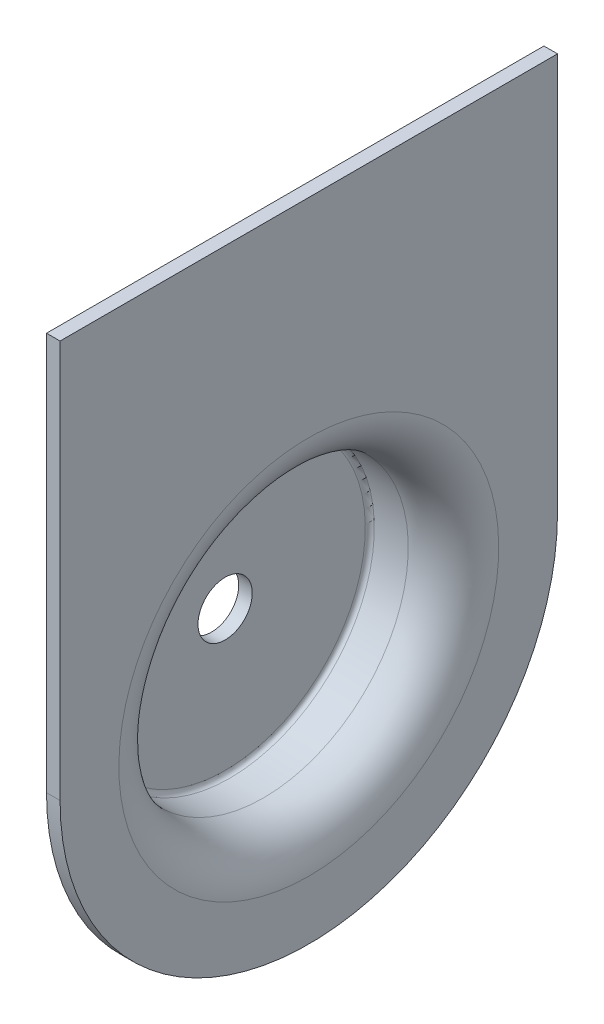
SolidWorks part; units mm, degrees
material "ABS"
ref_plane "Front Plane" through (0, 0, 0) normal (0, 0, 1) x (1, 0, 0)
ref_plane "Top Plane" through (0, 0, 0) normal (0, 1, 0) x (1, 0, 0)
ref_plane "Right Plane" through (0, 0, 0) normal (1, 0, 0) x (0, 0, -1)
sketch "Sketch1" plane through (-42.5, 0, 0) normal (1, 0, 0) x (0, 0, -1)
  circle A0 centre (50, -18.3727) radius 32
  arc A1 (50, 46.3864) -> (50, -83.1319) centre (50, -18.3727) ccw construction
  circle A6 centre (50, -18.3727) radius 31.5 construction
  circle A7 centre (50, -18.3727) radius 35
  dimension "D1" = 0.5
  dimension "D2" = 3
extrude "MOTOR RING" add sketch "Sketch1" against normal blind 6 and the other way offset from surface (12.5 mm away) 3
sketch "Sketch3" plane through (-48.5, 0, 0) normal (1, 0, 0) x (0, 0, -1)
  circle A0 centre (50, -18.3727) radius 6
  circle A1 centre (50, -18.3727) radius 35
  circle A2 centre (50, -18.3727) radius 35
  dimension "D2" = 12
  dimension "D1" = 0
extrude "MOTOR CAP" add sketch "Sketch3" against normal blind 3
sketch "Sketch2" plane through (-27, 0, 0) normal (-1, 0, 0) x (0, 0, 1)
  line L0 (-105, -18.3727) -> (-105, 69.6273)
  line L1 (-105, 69.6273) -> (5, 69.6273)
  line L2 (5, 69.6273) -> (5, -18.3727)
  arc A2 (-105, -18.3727) -> (5, -18.3727) centre (-50, -18.3727) ccw
  circle A4 centre (-50, -18.3727) radius 32 construction
  circle A5 centre (-50, -18.3727) radius 32
  point P4 (-190.8241, 50.9428)
extrude "BULK EXTRUDE" add sketch "Sketch2" along normal blind 3 from offset 3
fillet "Fillet2" radius 10 1 edges at (-33, -53.3727, -50)
fillet "Fillet3" radius 10 1 edges at (-30, -50.3727, -50)
fillet "Fillet4" radius 3 1 edges at (-51.5, 16.6273, -50)
fillet "Fillet5" radius 1 1 edges at (-48.5, 13.6273, -50)
